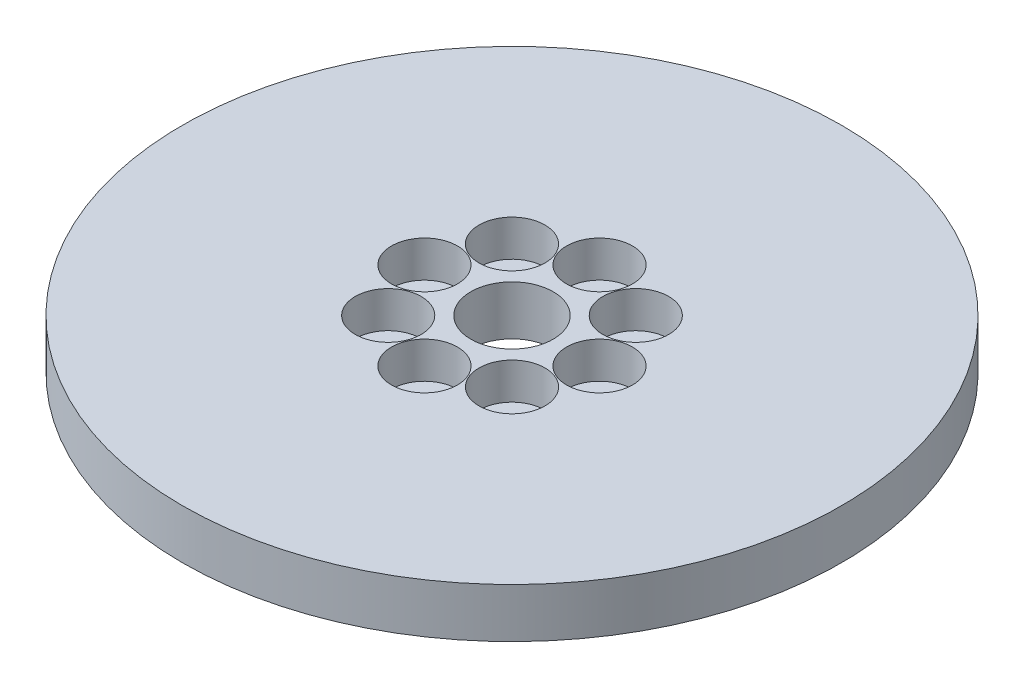
SolidWorks part; units mm, degrees
ref_plane "Front Plane" through (0, 0, 0) normal (0, 0, 1) x (1, 0, 0)
ref_plane "Top Plane" through (0, 0, 0) normal (0, 1, 0) x (1, 0, 0)
ref_plane "Right Plane" through (0, 0, 0) normal (1, 0, 0) x (0, 0, -1)
sketch "Sketch1" plane through (0, 0, 0) normal (0, 1, 0) x (1, 0, 0)
  circle A0 centre (0, 0) radius 100
  dimension "FLANGE_OD" = 200
extrude "Boss-Extrude1" add sketch "Sketch1" along normal blind 15
sketch "Sketch2" plane through (0, 0, 0) normal (0, 1, 0) x (1, 0, 0)
  circle A0 centre (0, 0) radius 12.5
  dimension "BORE_D" = 25
extrude "Cut-Extrude1" cut sketch "Sketch2" along normal through all
sketch "Sketch3" plane through (0, 15, 0) normal (0, 1, 0) x (1, 0, 0)
  circle A0 centre (0, 0) radius 26.5605 construction
  circle A1 centre (-26.5605, 0) radius 10
  dimension "BOLT_D" = 20
  dimension "BOLT_PCD" = 53.1209
extrude "Cut-Extrude2" cut sketch "Sketch3" against normal blind 11.0727
pattern_circular "CirPattern1" count 8 over 360 about axis through (0, 0, 0) along (0, 1, 0) of "Cut-Extrude2"
